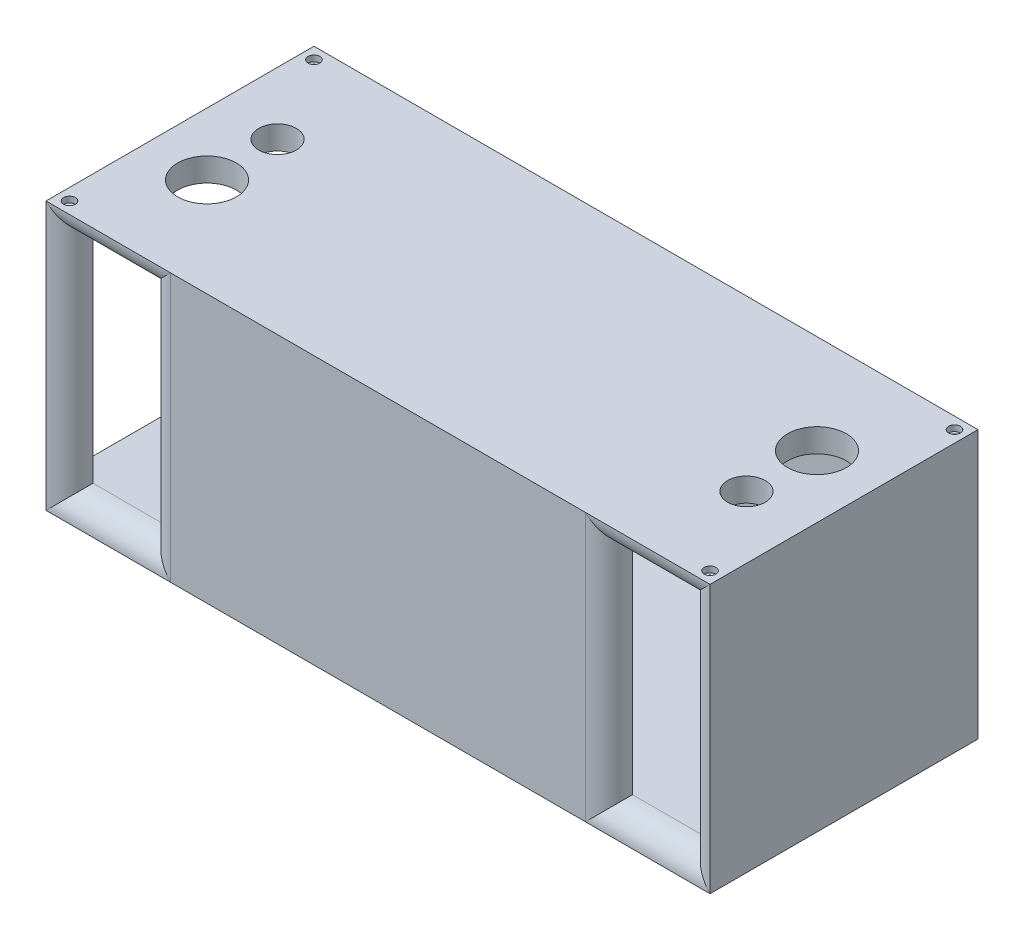
SolidWorks part; units mm, degrees
ref_plane "Front Plane" through (0, 0, 0) normal (0, 0, 1) x (1, 0, 0)
ref_plane "Top Plane" through (0, 0, 0) normal (0, 1, 0) x (1, 0, 0)
ref_plane "Right Plane" through (0, 0, 0) normal (1, 0, 0) x (0, 0, -1)
sketch "Sketch1" plane through (0, 0, 0) normal (0, 0, 1) x (1, 0, 0)
  line L0 (0, 0) -> (-282.5, 0)
  line L1 (-282.5, 0) -> (-282.5, 114)
  line L2 (-282.5, 114) -> (0, 114)
  line L3 (0, 114) -> (0, 0)
  dimension "D1" = 282.5
  dimension "D2" = 114
  dimension "D3" = 282.5
extrude "Boss-Extrude1" add sketch "Sketch1" along normal blind 114
ref_plane "Plane1" through (0, 0, 57) normal (0, 0, 1) x (1, 0, 0)
sketch "Sketch5" plane through (0, 0, 0) normal (0, 0, 1) x (1, 0, 0)
  line L0 (0, 114) -> (-282.5, 114) construction
  line L1 (-272.5, 104) -> (-239.5, 104)
  line L2 (-272.5, 104) -> (-272.5, 10)
  line L3 (-272.5, 10) -> (-239.5, 10)
  line L4 (-239.5, 104) -> (-239.5, 10)
  line L5 (-282.5, 114) -> (-282.5, 0) construction
  line L6 (-141.25, 114) -> (-141.25, 0) construction
  line L7 (-282.5, 0) -> (0, 0) construction
  line L8 (-10, 10) -> (-43, 10)
  line L9 (-43, 104) -> (-43, 10)
  line L10 (-10, 104) -> (-10, 10)
  line L11 (-10, 104) -> (-43, 104)
  dimension "D1" = 94
  dimension "D2" = 10
  dimension "D3" = 33
  dimension "D4" = 10
extrude "Cut-Extrude3" cut sketch "Sketch5" along normal through all
sketch "Sketch6" plane through (-282.5, 0, 0) normal (-1, 0, 0) x (0, 0, 1)
  line L0 (10, 104) -> (10, 10)
  line L1 (10, 10) -> (104, 10)
  line L2 (104, 10) -> (104, 104)
  line L3 (104, 104) -> (10, 104)
  line L4 (57, -62.7) -> (57, 62.7) construction
  line L5 (114, 114) -> (0, 114) construction
  dimension "D2" = 47
  dimension "D4" = 10
extrude "Cut-Extrude4" cut sketch "Sketch6" against normal blind 262
sketch "Sketch7" plane through (0, 114, 0) normal (0, 1, 0) x (1, 0, 0)
  line L1 (-282.5, -114) -> (-282.5, 0) construction
  line L3 (0, 0) -> (-282.5, 0) construction
  line L5 (-141.25, 0) -> (-141.25, -114) construction
  line L6 (0, -114) -> (-282.5, -114) construction
  line L7 (-282.5, -57) -> (0, -57) construction
  line L8 (0, -114) -> (0, 0) construction
  circle A0 centre (-277.5, -109) radius 1.25
  circle A1 centre (-277.5, -5) radius 1.25
  circle A2 centre (-5, -109) radius 1.25
  circle A3 centre (-5, -5) radius 1.25
extrude "Cut-Extrude5" cut sketch "Sketch7" against normal blind 262
sketch "Sketch8" plane through (0, 114, 0) normal (0, 1, 0) x (1, 0, 0)
  line L0 (-282.8751, -57) -> (-255.5296, -57) construction
  line L1 (-62.7, -57) -> (62.7, -57) construction
  circle A0 centre (-277.5, -5) radius 2.5
  circle A1 centre (-277.5, -109) radius 2.5
  circle A2 centre (-5, -5) radius 2.5
  circle A3 centre (-5, -109) radius 2.5
  dimension "D1" = 5
extrude "Cut-Extrude6" cut sketch "Sketch8" against normal blind 2.5
fillet "Fillet3" radius 10 1 edges at (-256, 104, 114)
fillet "Fillet4" radius 10 3 edges at (-239.5, 62, 114) (-272.5, 62, 114) (-256, 10, 114)
fillet "Fillet6" radius 10 12 edges at (-256, 104, 0) (-239.5, 57, 0) (-272.5, 57, 0) (-256, 10, 0) (-26.5, 10, 0) (-10, 57, 0) (-43, 57, 0) (-26.5, 104, 0) (-26.5, 10, 114) (-26.5, 104, 114) (-10, 57, 114) (-43, 57, 114)
sketch "Sketch11" plane through (0, 114, 0) normal (0, 1, 0) x (1, 0, 0)
  line L0 (-282.5, 0) -> (-229.5, 0) construction
  line L1 (-282.5, -3.9082) -> (-282.5, 0) construction
  line L2 (-282.5, 0) -> (-282.5, -114) construction
  line L3 (-256, 0) -> (-256, -114) construction
  line L4 (-229.5, -114) -> (-282.5, -114) construction
  line L5 (-256, 0) -> (-256, -42) construction
  line L6 (-256, -42) -> (-26.5, -42) construction
  line L9 (-277.5, -5) -> (-277.5, -10.9989) construction
  arc A0 (-282.5, -114) -> (-272.5, -104) centre (-282.5, -104) ccw construction
  circle A1 centre (-256, -42) radius 8
  circle A2 centre (-256, -72) radius 12.5
  circle A5 centre (-26.5, -42) radius 12.5
  circle A6 centre (-26.5, -72) radius 8
  dimension "D2" = 25
  dimension "D3" = 16
  dimension "D6" = 229.5
  dimension "D1" = 53
  dimension "D4" = 42
  dimension "D5" = 42
extrude "Cut-Extrude7" cut sketch "Sketch11" against normal blind 10
sketch "Sketch13" plane through (0, 114, 0) normal (0, 1, 0) x (1, 0, 0)
  line L0 (-5, -5) -> (-5, 0) construction
  line L2 (0, 0) -> (-53, 0) construction
